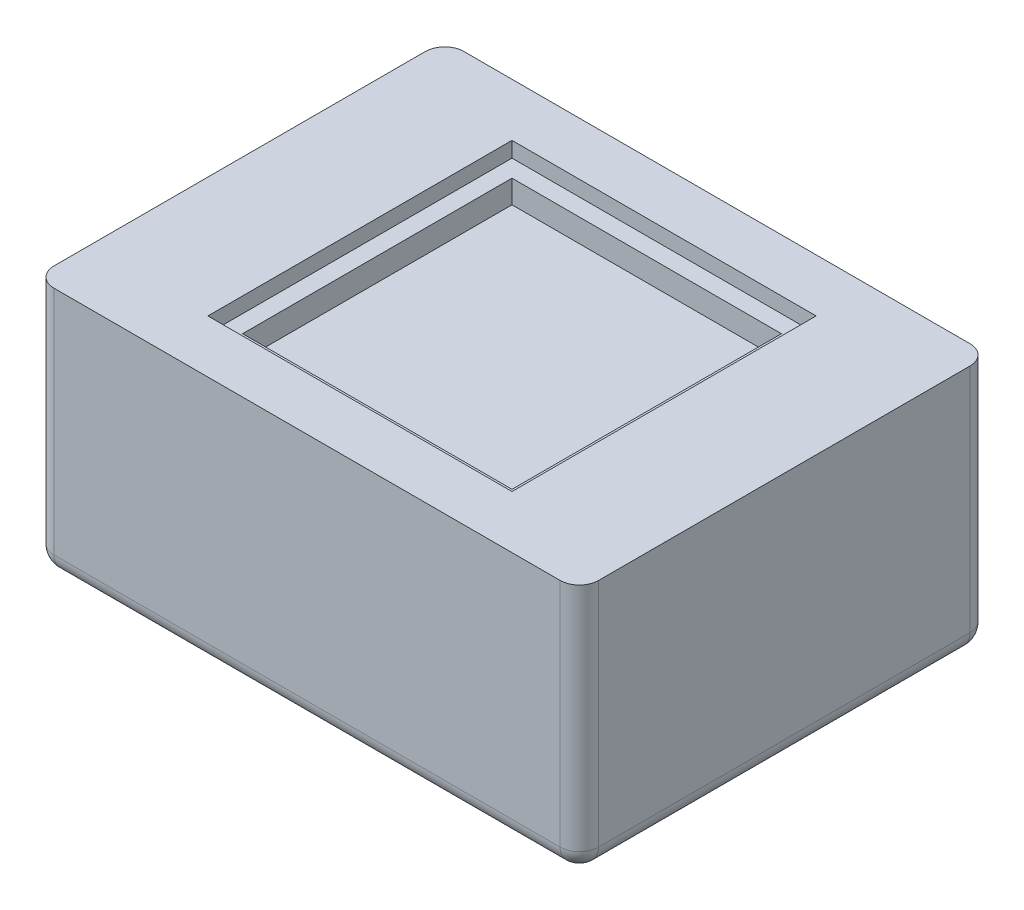
SolidWorks part; units mm, degrees
ref_plane "Front" through (0, 0, 0) normal (0, 0, 1) x (1, 0, 0)
ref_plane "Top" through (0, 0, 0) normal (0, 1, 0) x (1, 0, 0)
ref_plane "Right" through (0, 0, 0) normal (1, 0, 0) x (0, 0, -1)
sketch "草图1" plane through (0, 0, 0) normal (0, 1, 0) x (1, 0, 0)
  line L1 (-14.15, 10.65) -> (14.15, 10.65)
  line L2 (-14.15, 10.65) -> (-14.15, -10.65)
  line L3 (-14.15, -10.65) -> (14.15, -10.65)
  line L4 (14.15, 10.65) -> (14.15, -10.65)
  line L5 (-14.15, 10.65) -> (14.15, -10.65) construction
  line L6 (-14.15, -10.65) -> (14.15, 10.65) construction
  point P0 (0, 0)
  dimension "D1" = 21.3
  dimension "D2" = 28.3
extrude "凸台-拉伸1" add sketch "草图1" along normal blind 13
fillet "圆角1" radius 1 4 edges at (14.15, 6.5, 10.65) (-14.15, 6.5, 10.65) (-14.15, 6.5, -10.65) (14.15, 6.5, -10.65)
sketch "草图3" plane through (0, 13, 0) normal (0, 1, 0) x (1, 0, 0)
  line L1 (-7, 7) -> (7, 7)
  line L2 (-7, 7) -> (-7, -7)
  line L3 (-7, -7) -> (7, -7)
  line L4 (7, 7) -> (7, -7)
  line L5 (-7, 7) -> (7, -7) construction
  line L6 (-7, -7) -> (7, 7) construction
  point P0 (0, 0)
  dimension "D1" = 14
extrude "切除-拉伸2" cut sketch "草图3" against normal blind 2 contours L2 L1 L4 L3
sketch "草图4" plane through (0, 13, 0) normal (0, 1, 0) x (1, 0, 0)
  line L0 (-7, -7) -> (7, -7) construction
  line L1 (-7.9, 7.9) -> (7.9, 7.9)
  line L2 (-7.9, 7.9) -> (-7.9, -7.9)
  line L3 (-7.9, -7.9) -> (7.9, -7.9)
  line L4 (7.9, 7.9) -> (7.9, -7.9)
  line L5 (-7.9, 7.9) -> (7.9, -7.9) construction
  line L6 (-7.9, -7.9) -> (7.9, 7.9) construction
  point P0 (0, 0)
  dimension "D1" = 0.9
extrude "切除-拉伸3" cut sketch "草图4" against normal blind 0.8 contours L2 L1 L4 L3
fillet "圆角2" radius 1 8 edges at (0, 0, -10.65) (14.15, 0, 0) (13.8571, 0, 10.3571) (13.8571, 0, -10.3571) (-13.8571, 0, -10.3571) (-13.8571, 0, 10.3571) (0, 0, 10.65) (-14.15, 0, 0)
